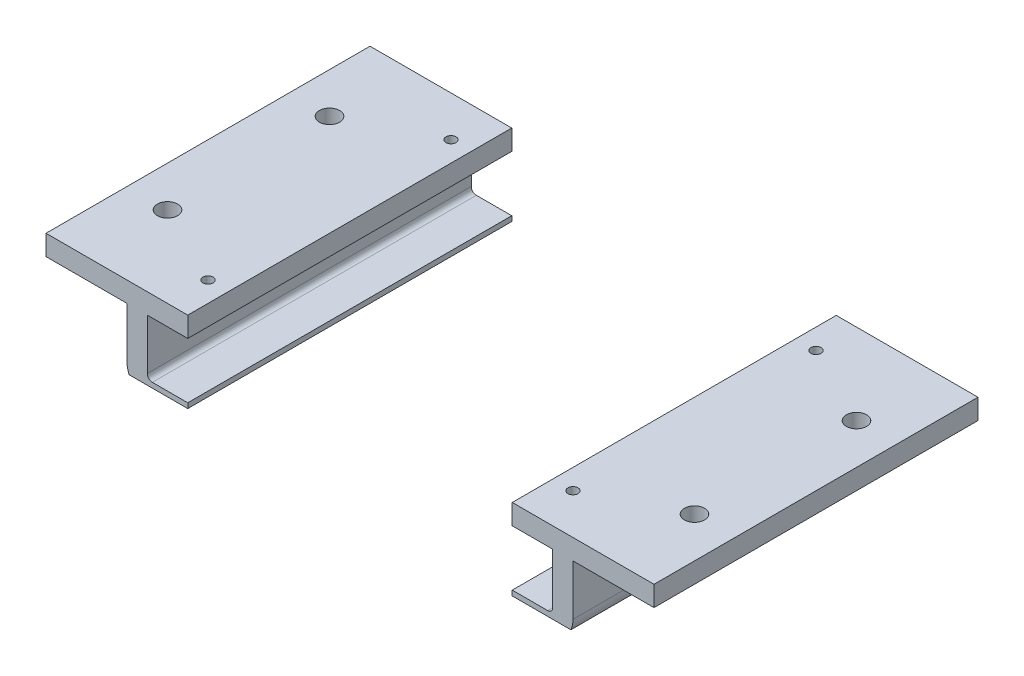
SolidWorks part; units mm, degrees
material "ABS"
ref_plane "Front" through (0, 0, 0) normal (0, 0, 1) x (1, 0, 0)
ref_plane "Top" through (0, 0, 0) normal (0, 1, 0) x (1, 0, 0)
ref_plane "Right" through (0, 0, 0) normal (1, 0, 0) x (0, 0, -1)
sketch "Sketch1" plane through (0, 0, 0) normal (0, 0, 1) x (1, 0, 0)
  line L0 (69.9262, 17.4625) -> (69.9262, 1.5875)
  line L1 (50.8762, 23.8125) -> (95.3262, 23.8125)
  line L3 (50.8762, -1.5875) -> (50.8762, 0)
  line L4 (50.8762, 0) -> (61.9887, 0)
  line L5 (63.5762, 1.5875) -> (63.5762, 17.4625)
  line L6 (63.5762, 17.4625) -> (50.8762, 17.4625)
  line L7 (50.8762, 17.4625) -> (50.8762, 23.8125)
  line L8 (0, 1.8543) -> (0, -12.2758) construction
  line L18 (95.3262, 23.8125) -> (95.3262, 17.4625)
  line L19 (95.3262, 17.4625) -> (69.9262, 17.4625)
  line L20 (50.8762, -1.5875) -> (69.2635, -1.5875)
  line L21 (69.9262, 1.5875) -> (63.5762, 1.5875) construction
  arc A1 (69.2635, -1.5875) -> (69.9262, 1.5875) centre (61.9887, 1.5875) ccw
  arc A2 (61.9887, 0) -> (63.5762, 1.5875) centre (61.9887, 1.5875) ccw
  point P0 (0, 0)
  point P18 (0, 17.4625)
  line B0 (-61.9887, 0) -> (61.9887, 0)
  line B1 (-63.5762, 17.4625) -> (-63.5762, 1.5875)
  line B2 (63.5762, 1.5875) -> (63.5762, 17.4625)
  line B3 (63.5762, 17.4625) -> (-63.5762, 17.4625)
  arc B4 (61.9887, 0) -> (63.5762, 1.5875) centre (61.9887, 1.5875) ccw
  arc B5 (-63.5762, 1.5875) -> (-61.9887, 0) centre (-61.9887, 1.5875) ccw
  dimension "D1" = 12.7
  dimension "D2" = 12.7
  dimension "D3" = 6.35
  dimension "D4" = 25.4
  dimension "D5" = 1.5875
sketch_block_instance "Block-Sensor Back View-1"
sketch_block "Block-Sensor Back View"
extrude "Boss-Extrude2" add sketch "Sketch1" against normal blind 101.6 contours A2 L4 L3 A1 L0 L19 L18 L1 L7 L6 L5 region at (69.4142, 9.525, 0)
sketch "Sketch2" plane through (0, 23.8125, 0) normal (0, 1, 0) x (1, 0, 0)
  line L0 (57.2262, 88.9) -> (57.2262, 12.7) construction
  line L1 (82.6262, 101.6) -> (82.6262, 0) construction
  line L4 (50.8762, 0) -> (95.3262, 0)
  line L5 (95.3262, 0) -> (95.3262, 101.6)
  line L6 (95.3262, 101.6) -> (50.8762, 101.6)
  line L7 (50.8762, 101.6) -> (50.8762, 0)
  line L8 (50.8762, 0) -> (95.3262, 0) construction
  line L9 (95.3262, 0) -> (95.3262, 101.6) construction
  line L10 (95.3262, 101.6) -> (50.8762, 101.6) construction
  line L11 (50.8762, 101.6) -> (50.8762, 0) construction
  circle A0 centre (57.2262, 88.9) radius 1.5875
  circle A1 centre (57.2262, 12.7) radius 1.5875
  circle A2 centre (82.6262, 76.2) radius 3.175
  circle A3 centre (82.6262, 25.4) radius 3.175
  point P10 (57.2262, 50.8)
  point P15 (82.6262, 50.8)
  dimension "D2" = 3.175
  dimension "D8" = 6.35
  dimension "D3" = 12.7
  dimension "D4" = 6.35
  dimension "D5" = 12.7
  dimension "D6" = 25.4
  dimension "D7" = 25.4
  dimension "D1" = 0
extrude "Cut-Extrude1" cut sketch "Sketch2" against normal up to next
ref_plane "MidPlane" through (0, 0, 0) normal (-1, 0, 0) x (0, 0, 1)
mirror "Mirror5" about plane through (0, 0, 0) normal (-1, 0, 0) of bodies 104
